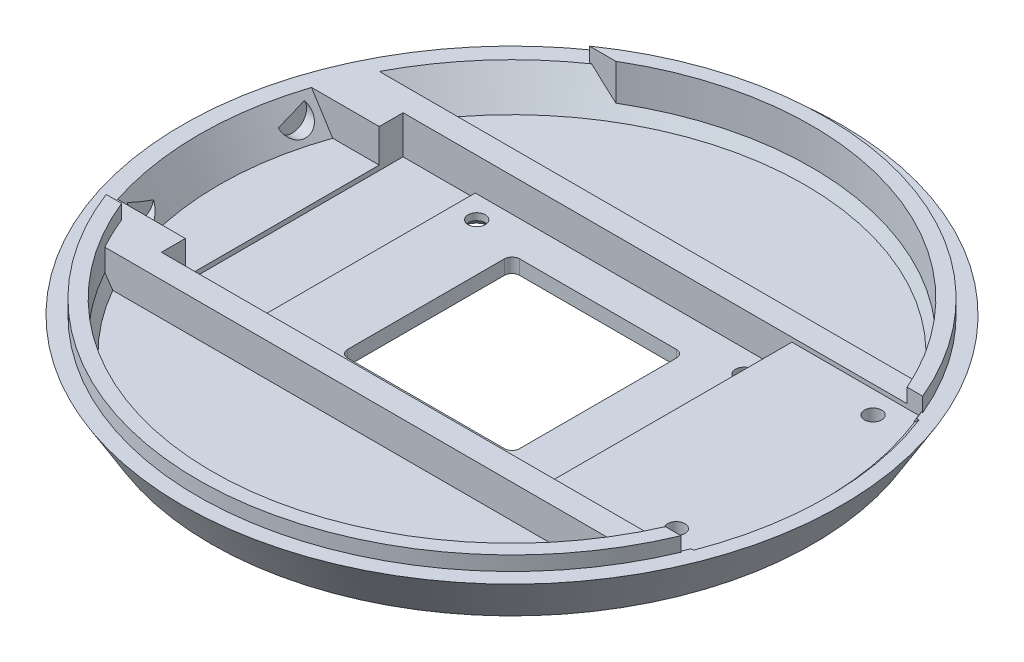
SolidWorks part; units mm, degrees
ref_plane "Front Plane" through (0, 0, 0) normal (0, 0, 1) x (1, 0, 0)
ref_plane "Top Plane" through (0, 0, 0) normal (0, 1, 0) x (1, 0, 0)
ref_plane "Right Plane" through (0, 0, 0) normal (1, 0, 0) x (0, 0, -1)
sketch "Sketch1" plane through (0, 0, 0) normal (0, 0, 1) x (1, 0, 0)
  line L0 (0, 0) -> (63, 0)
  line L1 (63, 0) -> (69, 10)
  line L6 (0, 3) -> (61.3014, 3)
  line L7 (61.3014, 3) -> (65.5014, 10)
  line L8 (69, 10) -> (65.5014, 10)
  line L9 (0, 0) -> (0, 3)
  line L10 (61.3014, 3) -> (66.4275, 11.5435) construction
  dimension "D1" = 69
  dimension "D2" = 63
  dimension "D3" = 10
  dimension "D4" = 3
revolve "Revolve1" add sketch "Sketch1" angle 360 about L9
sketch "Sketch2" plane through (0, 3, 0) normal (0, 1, 0) x (1, 0, 0)
  line L1 (-18, 18) -> (18, 18)
  line L2 (-18, 18) -> (-18, -18)
  line L3 (-18, -18) -> (18, -18)
  line L4 (18, 18) -> (18, -18)
  line L5 (-18, 18) -> (18, -18) construction
  line L6 (-18, -18) -> (18, 18) construction
  point P0 (0, 0)
  dimension "D1" = 36
  dimension "D2" = 36
  dimension "D12" = 0
  dimension "D13" = 0
extrude "Cut-Extrude1" cut sketch "Sketch2" against normal through all
fillet "Fillet1" radius 1.6 4 edges at (18, 1.5, -18) (18, 1.5, 18) (-18, 1.5, 18) (-18, 1.5, -18)
hole_wizard "CSK for M3 Countersunk Flat Head Screw2" positions "3DSketch3" profile "Sketch6" countersink size "M3" standard "ISO" end condition through all
sketch3d "3DSketch3"
  line L0 (16.4, 0, -18) -> (-16.4, 0, -18) construction
  line L1 (-16.4, 0, 18) -> (16.4, 0, 18) construction
  line L2 (18, 0, 16.4) -> (18, 0, -16.4) construction
  line L3 (-18, 0, -16.4) -> (-18, 0, 16.4) construction
  point P0 (-28, 0, -20.6)
  point P2 (-28, 0, 20.6)
  point P4 (28, 0, 20.6)
  point P6 (28, 0, -20.6)
  point P23 (0, 0, 0)
  point P24 (0, 0, 0)
  point P25 (0, 0, 0)
  dimension "D1" = 2.6
  dimension "D2" = 2.6
  dimension "D3" = 2.6
  dimension "D4" = 2.6
  dimension "D5" = 10
  dimension "D6" = 10
  dimension "D7" = 10
  dimension "D8" = 10
sketch "Sketch6" plane through (-28, 0, -20.6) normal (1, 0, 0) x (0, 0, -1)
  line L0 (0, 0) -> (0, 10)
  line L1 (0, 10) -> (1.8, 10)
  line L2 (1.8, 10) -> (1.8, 1.55)
  line L3 (1.8, 1.55) -> (3.35, 0)
  line L5 (3.35, 0) -> (0, 0)
  line L6 (-1.8, 1.55) -> (-3.35, 0) construction
  line L11 (0, -6.35) -> (0, 107.95) construction
  dimension "Thru Hole Dia." = 3.6
  dimension "Thru Hole Depth" = 10
  dimension "Near C'Sink Dia." = 6.7
  dimension "Near C'Sink Angle" = 90
sketch "Sketch19" plane through (0, 3, 0) normal (0, 1, 0) x (1, 0, 0)
  line L0 (-33, 25) -> (-33, -25) construction
  line L1 (-48.1, 25.3) -> (-33, 25.3)
  line L2 (-48.1, 25.3) -> (-48.1, -25.3)
  line L3 (-48.1, -25.3) -> (-33, -25.3)
  line L4 (-33, 25.3) -> (-33, -25.3)
  line L5 (-47.8, 45.1467) -> (-47.8, -23.3) construction
  line L6 (-33.3, 25) -> (-47.8, 25) construction
  line L7 (-33.3, -25) -> (-47.8, -25) construction
  dimension "D1" = 0.3
  dimension "D2" = 0.3
  dimension "D3" = 0.3
extrude "Cut-Extrude4" cut sketch "Sketch19" against normal blind 1
sketch "Sketch21" plane through (0, 0, 0) normal (1, 0, 0) x (0, 0, -1)
  line L3 (-25.3, 3) -> (25.3, 3)
  line L6 (25.3, 3) -> (25.3, 9.1)
  line L7 (25.3, 9.1) -> (-25.3, 9.1)
  line L8 (-25.3, 9.1) -> (-25.3, 3)
  dimension "D1" = 0
  dimension "D2" = 0.3
  dimension "D3" = 0.3
  dimension "D4" = 0
extrude "Boss-Extrude1" add sketch "Sketch21" along normal up to next from offset 33.3
sketch "Sketch22" plane through (0, 0, 0) normal (1, 0, 0) x (0, 0, -1)
  line L0 (65.5014, 10) -> (-65.5014, 10) construction
  line L1 (-30.3, 10) -> (-25.3, 10)
  line L2 (-30.3, 10) -> (-30.3, 3)
  line L3 (-30.3, 3) -> (-25.3, 3)
  line L4 (-25.3, 10) -> (-25.3, 3)
  line L5 (25.3, 10) -> (30.3, 10)
  line L6 (25.3, 10) -> (25.3, 3)
  line L7 (25.3, 3) -> (30.3, 3)
  line L8 (30.3, 10) -> (30.3, 3)
  dimension "D1" = 0
  dimension "D2" = 0
  dimension "D3" = 5
  dimension "D4" = 5
  dimension "D5" = 0
  dimension "D6" = 0
  dimension "D7" = 0
  dimension "D8" = 0
extrude "Boss-Extrude2" add sketch "Sketch22" along normal up to next and the other way up to next
sketch "Sketch23" plane through (0, 0, 0) normal (1, 0, 0) x (0, 0, -1)
  line L0 (20, 39) -> (20, 7) construction
  line L1 (25.3, 10) -> (20.3, 10)
  line L2 (25.3, 10) -> (25.3, 3)
  line L3 (25.3, 3) -> (20.3, 3)
  line L4 (20.3, 10) -> (20.3, 3)
  line L5 (-25.3, 10) -> (-20.3, 10)
  line L6 (-25.3, 10) -> (-25.3, 3)
  line L7 (-25.3, 3) -> (-20.3, 3)
  line L8 (-20.3, 10) -> (-20.3, 3)
  line L9 (-20, 7) -> (-20, 39) construction
  dimension "D1" = 0.3
  dimension "D2" = 0.3
  dimension "D3" = 0
  dimension "D4" = 0
  dimension "D5" = 0
  dimension "D6" = 0
  dimension "D7" = 0
  dimension "D8" = 0
extrude "Boss-Extrude3" add sketch "Sketch23" against normal up to next from offset 48.1 offset against normal yes
sketch "Sketch24" plane through (0, 10, 0) normal (0, 1, 0) x (1, 0, 0)
  line L0 (-32.1302, 53.9) -> (-37.6544, 53.9)
  line L1 (57.4236, -25.3) -> (60.6875, -25.3)
  line L2 (-58.1429, -23.6) -> (-61.3686, -23.6)
  line L3 (-61.7504, -23.3) -> (-58.1, -23.3) construction
  line L4 (57.4236, 25.3) -> (60.6875, 25.3)
  line L7 (60.8117, -25) -> (-47.8, -25) construction
  line L8 (-47.8, 25) -> (60.8117, 25) construction
  arc A0 (-61.3686, -23.6) -> (60.6875, -25.3) centre (0, 0) ccw
  arc A1 (-58.1429, -23.6) -> (57.4236, -25.3) centre (0, 0) ccw
  arc A2 (57.4236, 25.3) -> (-32.1302, 53.9) centre (0, 0) ccw
  arc A3 (60.6875, 25.3) -> (-37.6544, 53.9) centre (0, 0) ccw
  dimension "D1" = 131.5
  dimension "D2" = 125.5
  dimension "D3" = 0.3
  dimension "D4" = 0
  dimension "D5" = 0.3
  dimension "D6" = 0.3
extrude "Boss-Extrude4" add sketch "Sketch24" along normal blind 3 and the other way up to next
sketch "Sketch25" plane through (0, 10, 0) normal (0, 1, 0) x (1, 0, 0)
  line L0 (61.6364, 23.6) -> (60, 23.6)
  line L1 (60, 23.6) -> (60, -23.6)
  line L2 (60, -23.6) -> (61.6364, -23.6)
  line L3 (61.4831, 23.3) -> (23.9318, 23.3) construction
  line L4 (-47.8, -23.3) -> (61.4831, -23.3) construction
  arc A0 (61.6364, -23.6) -> (61.6364, 23.6) centre (0, 0) ccw
  dimension "D1" = 132
  dimension "D2" = 0.3
  dimension "D3" = 0.3
  dimension "D4" = 60
extrude "Cut-Extrude5" cut sketch "Sketch25" against normal blind 0.9
chamfer "Chamfer1" distance 0.9 angle 45 1 edges at (66, 9.1, 0)
sketch "Sketch26" plane through (0, 0, 0) normal (1, 0, 0) x (0, 0, -1)
  circle A2 centre (-16, 7) radius 3
  circle A3 centre (16, 7) radius 3
  dimension "D3" = 6
  dimension "D1" = 16
  dimension "D4" = 6
  dimension "D2" = 16
extrude "Cut-Extrude6" cut sketch "Sketch26" against normal blind 4 from offset 58 offset against normal yes
hole_wizard "CSK for M3 Countersunk Flat Head Screw3" positions "Sketch27" profile "Sketch28" countersink size "M3" standard "ISO" end condition through all
sketch "Sketch27" plane through (0, 0, 0) normal (0, -1, 0) x (-1, 0, 0)
  line L0 (16.4, -18) -> (-16.4, -18) construction
  line L1 (-16.4, 18) -> (16.4, 18) construction
  line L2 (-18, -16.4) -> (-18, 16.4) construction
  point P0 (-55, 20.6)
  point P2 (-55, -20.6)
  dimension "D1" = 2.6
  dimension "D2" = 2.6
  dimension "D3" = 37
  dimension "D4" = 37
sketch "Sketch28" plane through (55, 0, -20.6) normal (1, 0, 0) x (0, 0, -1)
  line L0 (0, 0) -> (0, 13)
  line L1 (0, 13) -> (1.8, 13)
  line L2 (1.8, 13) -> (1.8, 1.55)
  line L3 (1.8, 1.55) -> (3.35, 0)
  line L5 (3.35, 0) -> (0, 0)
  line L6 (-1.8, 1.55) -> (-3.35, 0) construction
  line L11 (0, -6.35) -> (0, 107.95) construction
  dimension "Thru Hole Dia." = 3.6
  dimension "Thru Hole Depth" = 13
  dimension "Near C'Sink Dia." = 6.7
  dimension "Near C'Sink Angle" = 90
